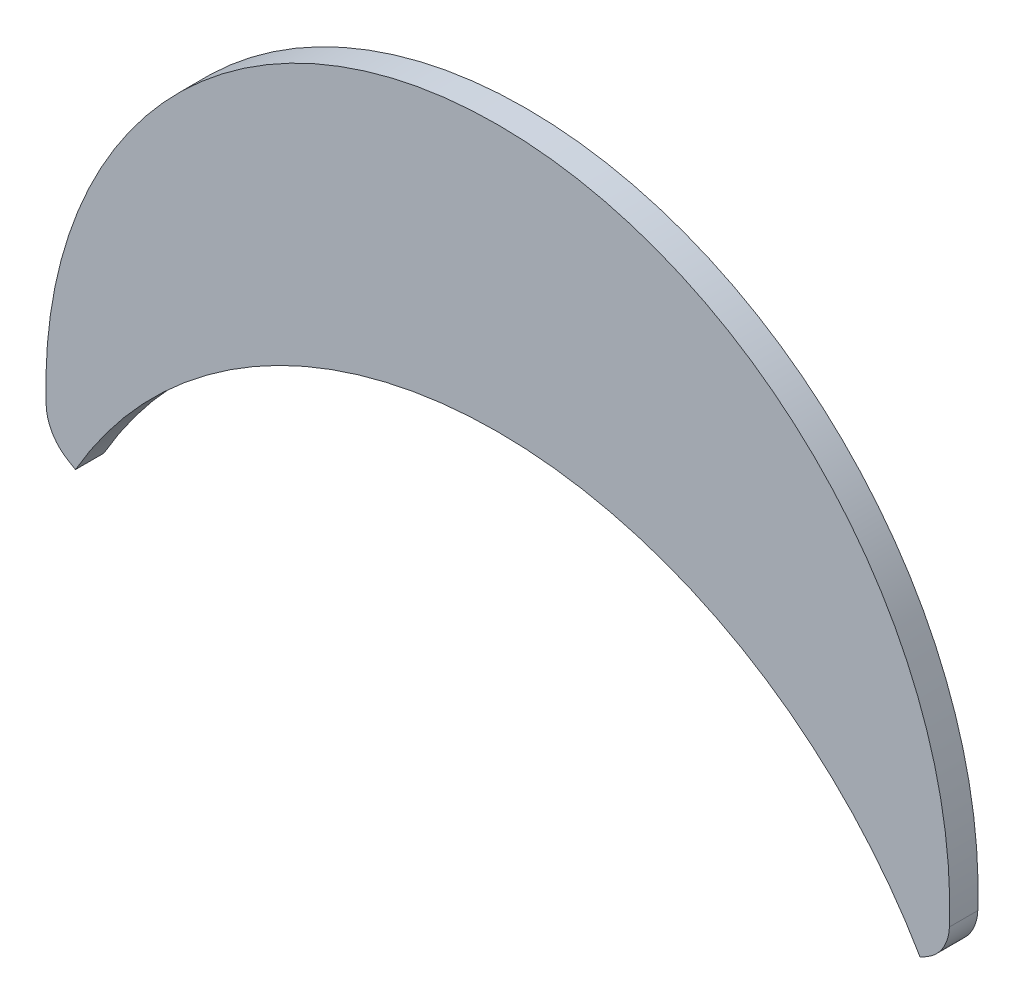
SolidWorks part; units mm, degrees
material "AISI 4130 Steel, annealed at 865C"
ref_plane "Plane1" through (0, 0, 0) normal (0, 0, 1) x (1, 0, 0)
ref_plane "Plane2" through (0, 0, 0) normal (0, 1, 0) x (1, 0, 0)
ref_plane "Plane3" through (0, 0, 0) normal (1, 0, 0) x (0, 0, -1)
ref_axis "Axis1" through (-83.9706, 0, 0) along (1, 0, 0)
ref_axis "Axis2" through (0, 0, -14.8431) along (0, 0, 1)
ref_axis "Axis3" through (0, 28.3369, 0) along (0, -1, 0)
sketch "Sketch1" plane through (0, 0, 0) normal (0, 0, 1) x (1, 0, 0)
  line L0 (0, 0) -> (23.3719, 13.4937) construction
  line L1 (0, 0) -> (-23.3719, 13.4937) construction
  line L2 (-23.3719, 13.4937) -> (-15.123, 8.7312)
  line L3 (15.123, 8.7312) -> (23.3719, 13.4937)
  line L4 (0, 0) -> (0, 26.9875) construction
  arc A0 (23.3719, 13.4937) -> (-23.3719, 13.4937) centre (0, 0) ccw
  arc A1 (15.123, 8.7312) -> (-15.123, 8.7312) centre (0, 0) ccw
  dimension "D1" = 17.4625
  dimension "D3" = 120
  dimension "D2" = 9.525
extrude "Boss-Extrude1" add sketch "Sketch1" along normal blind 1.016
sketch "Sketch2" plane through (0, 0, 1.016) normal (0, 0, 1) x (1, 0, 0)
  line L0 (-23.3719, 13.4937) -> (-15.123, 8.7312) construction
  line L1 (15.123, 8.7312) -> (23.3719, 13.4937) construction
  line L2 (0, 0) -> (0, 17.4625) construction
  line L3 (-16.1128, 9.3027) -> (-15.123, 8.7312)
  line L4 (16.1128, 9.3027) -> (15.123, 8.7312)
  arc A0 (-16.1128, 9.3027) -> (16.1128, 9.3027) centre (0, 10.8048) cw
  arc A1 (23.3719, 13.4937) -> (-23.3719, 13.4937) centre (0, 0) ccw construction
  arc A2 (15.123, 8.7312) -> (-15.123, 8.7312) centre (0, 0) ccw construction
  arc A3 (15.123, 8.7312) -> (-15.123, 8.7312) centre (0, 0) ccw
  dimension "D1" = 1.143
extrude "Cut-Extrude1" cut sketch "Sketch2" against normal through all flip side to cut
fillet "Fillet1" radius 1.5875 2 edges at (16.1128, 9.3027, 0.508) (-16.1128, 9.3027, 0.508)
sketch "Sketch3" plane through (0, 0, 1.016) normal (0, 0, 1) x (1, 0, 0)
  line L0 (0, 3.175) -> (0, 0) construction
  line L1 (-15.875, 3.175) -> (15.875, 3.175)
  line L2 (-15.875, 3.175) -> (-15.875, 25.4)
  line L3 (-15.875, 25.4) -> (15.875, 25.4)
  line L4 (15.875, 3.175) -> (15.875, 25.4)
  line L5 (-15.875, 3.175) -> (15.875, 25.4) construction
  line L6 (-15.875, 25.4) -> (15.875, 3.175) construction
  line L7 (0, 14.2875) -> (7.9375, 14.2875) construction
  circle A0 centre (7.9375, 14.2875) radius 1.4478
  circle A1 centre (-7.9375, 14.2875) radius 1.4478
  point P0 (0, 14.2875)
  dimension "D4" = 2.8956
  dimension "D1" = 31.75
  dimension "D2" = 22.225
  dimension "D3" = 3.175
  dimension "D5" = 15.875
equation "\"D1@Sketch1\"=1.375/2"
